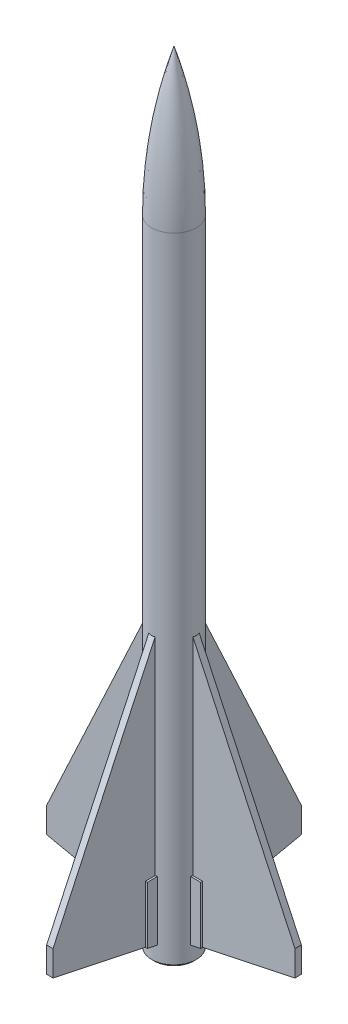
SolidWorks part; units mm, degrees
ref_plane "Alzado" through (0, 0, 0) normal (0, 0, 1) x (1, 0, 0)
ref_plane "Planta" through (0, 0, 0) normal (0, 1, 0) x (1, 0, 0)
ref_plane "Vista lateral" through (0, 0, 0) normal (1, 0, 0) x (0, 0, -1)
sketch "Croquis2" plane through (0, 0, 0) normal (0, 0, 1) x (1, 0, 0)
  line L0 (0, 0) -> (0, 615)
  line L2 (17.5, 500) -> (17.5, 0)
  line L3 (17.5, 0) -> (0, 0)
  arc A0 (17.5, 500) -> (0, 615) centre (-369.1071, 500) ccw
  dimension "D1" = 615
  dimension "D2" = 17.5
  dimension "D3" = 500
revolve "Revolución1" add sketch "Croquis2" angle 360 about L0
sketch "Croquis3" plane through (0, 0, 0) normal (0, 0, 1) x (1, 0, 0)
  line L0 (0, 10) -> (-97.579, 30.7411)
  line L2 (-97.579, 50.7411) -> (0, 260)
  line L3 (0, 260) -> (0, 10)
  line L4 (-97.579, 30.7411) -> (-97.579, 50.7411)
  line L5 (-17.5, 0) -> (17.5, 0) construction
  dimension "D1" = 12
  dimension "D2" = 25
  dimension "D3" = 250
  dimension "D4" = 10
  dimension "D5" = 20
extrude "Saliente-Extruir1" add sketch "Croquis3" along normal mid plane 5
sketch "Croquis4" plane through (0, 0, 0) normal (0, 0, 1) x (1, 0, 0)
  line L0 (-25, 15.3139) -> (-25, 60.3139)
  line L1 (-97.579, 30.7411) -> (-17.3205, 13.6816) construction
  line L2 (-25, 60.3139) -> (0, 60.3139)
  line L3 (0, 60.3139) -> (0, 10)
  line L4 (0, 10) -> (-25, 15.3139)
  point P5 (4.7779, 9.4404)
  point P8 (0, 0)
  dimension "D1" = 45
  dimension "D2" = 25
extrude "Saliente-Extruir2" add sketch "Croquis4" along normal mid plane 8
ref_axis "Eje1" through (0, 645.75, 0) along (0, -1, 0)
pattern_circular "MatrizC2" count 4 over 360 about axis through (0, 645.75, 0) along (0, -1, 0) of "Saliente-Extruir1", "Saliente-Extruir2"
chamfer "Chaflán1" distance 2 angle 45 1 edges at (0, 0, -17.5)
